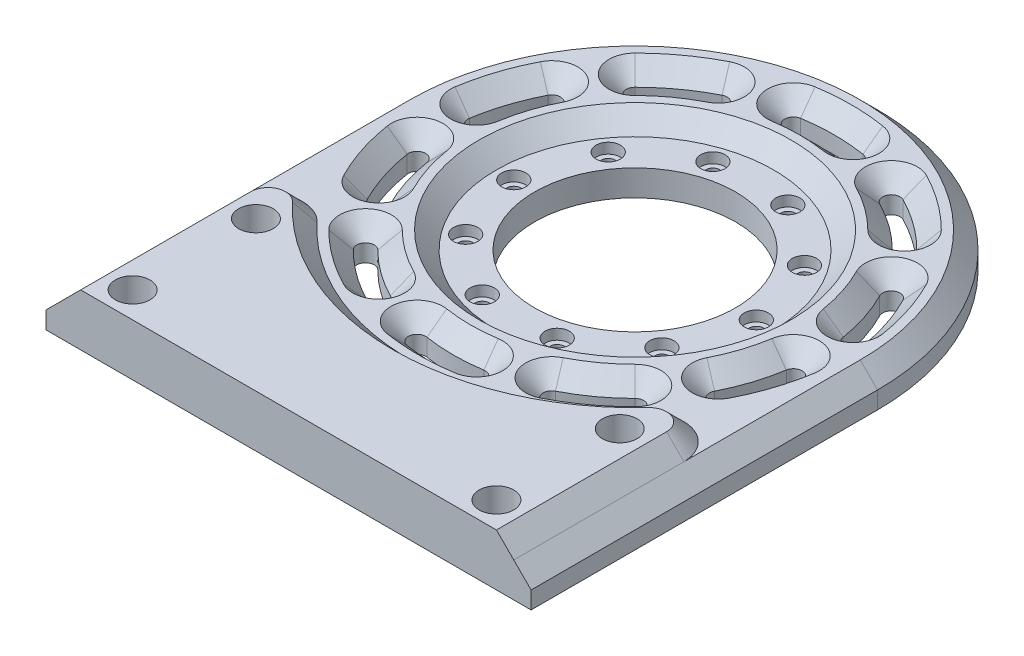
SolidWorks part; units mm, degrees
ref_plane "Front Plane" through (0, 0, 0) normal (0, 0, 1) x (1, 0, 0)
ref_plane "Top Plane" through (0, 0, 0) normal (0, 1, 0) x (1, 0, 0)
ref_plane "Right Plane" through (0, 0, 0) normal (1, 0, 0) x (0, 0, -1)
sketch "Sketch1" plane through (0, 0, 0) normal (0, 1, 0) x (1, 0, 0)
  line L0 (-70, 0) -> (-70, -100)
  line L1 (70, 0) -> (70, -100)
  line L2 (0, -100) -> (70, -100)
  line L3 (0, -100) -> (-70, -100)
  circle A2 centre (0, 0) radius 70
  circle A3 centre (0, 0) radius 29
  circle A4 centre (0, 0) radius 40
  circle A5 centre (-35, 0) radius 2
  circle A6 centre (-28.3156, 20.5725) radius 2
  circle A7 centre (-10.8156, 33.287) radius 2
  circle A8 centre (10.8156, 33.287) radius 2
  circle A9 centre (28.3156, 20.5725) radius 2
  circle A10 centre (35, 0) radius 2
  circle A11 centre (28.3156, -20.5725) radius 2
  circle A12 centre (10.8156, -33.287) radius 2
  circle A13 centre (-10.8156, -33.287) radius 2
  circle A14 centre (-28.3156, -20.5725) radius 2
  circle A15 centre (0, 0) radius 35
  point P36 (0, 0)
  dimension "D1" = 10
extrude "Boss-Extrude2" add sketch "Sketch1" along normal blind 10 contours A12 A15 A11 A10 A9 A8 A7 A6 A5 A14 A13 A3 | A4 A15 A12 A13 A14 A5 A6 A7 A8 A9 A10 A11 | A2 A4 | A2 L0 L3 L2 L1 region at (0, 0, 74.778) region at (0, 0, -68.0201) region at (-38.8686, 0, 0) region at (-32.8564, 0, -2.0832)
sketch "Sketch4" plane through (0, 10, 0) normal (0, 1, 0) x (1, 0, 0)
  circle A0 centre (0, 0) radius 29
  circle A1 centre (0, 0) radius 40
extrude "Cut-Extrude5" cut sketch "Sketch4" against normal blind 5
chamfer "Chamfer11" distance 5 angle 45 4 edges at (70, 10, 50) (0, 10, -70) (-70, 10, 50) (0, 10, 40)
sketch "Sketch7" plane through (0, 10, 0) normal (0, 1, 0) x (1, 0, 0)
  line L0 (0, 0) -> (-55, 0)
  line L1 (0, 0) -> (-28.3156, 20.5725)
  line L2 (-28.3156, 20.5725) -> (-44.4959, 32.3282)
  line L3 (0, 0) -> (-54.3229, 8.6039)
  line L4 (0, 0) -> (-52.3081, 16.9959)
  line L5 (0, 0) -> (-49.0054, 24.9695)
  circle A0 centre (0, 0) radius 55
  arc A1 (-49.0054, 24.9695) -> (-54.3229, 8.6039) centre (0, 0) ccw construction
  arc A2 (-51.2329, 26.1045) -> (-56.7921, 8.995) centre (0, 0) ccw
  arc A3 (-46.7778, 23.8345) -> (-51.8536, 8.2128) centre (0, 0) ccw
  arc A4 (-46.7778, 23.8345) -> (-51.2329, 26.1045) centre (-49.0054, 24.9695) ccw
  arc A5 (-56.7921, 8.995) -> (-51.8536, 8.2128) centre (-54.3229, 8.6039) ccw
  arc A6 (-24.9695, 49.0054) -> (-38.8909, 38.8909) centre (0, 0) ccw construction
  arc A7 (-26.1045, 51.2329) -> (-40.6586, 40.6586) centre (0, 0) ccw
  arc A8 (-23.8345, 46.7778) -> (-37.1231, 37.1231) centre (0, 0) ccw
  arc A9 (-23.8345, 46.7778) -> (-26.1045, 51.2329) centre (-24.9695, 49.0054) ccw
  arc A10 (-40.6586, 40.6586) -> (-37.1231, 37.1231) centre (-38.8909, 38.8909) ccw
  arc A11 (8.6039, 54.3229) -> (-8.6039, 54.3229) centre (0, 0) ccw construction
  arc A12 (8.995, 56.7921) -> (-8.995, 56.7921) centre (0, 0) ccw
  arc A13 (8.2128, 51.8536) -> (-8.2128, 51.8536) centre (0, 0) ccw
  arc A14 (8.2128, 51.8536) -> (8.995, 56.7921) centre (8.6039, 54.3229) ccw
  arc A15 (-8.995, 56.7921) -> (-8.2128, 51.8536) centre (-8.6039, 54.3229) ccw
  arc A16 (38.8909, 38.8909) -> (24.9695, 49.0054) centre (0, 0) ccw construction
  arc A17 (40.6586, 40.6586) -> (26.1045, 51.2329) centre (0, 0) ccw
  arc A18 (37.1231, 37.1231) -> (23.8345, 46.7778) centre (0, 0) ccw
  arc A19 (37.1231, 37.1231) -> (40.6586, 40.6586) centre (38.8909, 38.8909) ccw
  arc A20 (26.1045, 51.2329) -> (23.8345, 46.7778) centre (24.9695, 49.0054) ccw
  arc A21 (54.3229, 8.6039) -> (49.0054, 24.9695) centre (0, 0) ccw construction
  arc A22 (56.7921, 8.995) -> (51.2329, 26.1045) centre (0, 0) ccw
  arc A23 (51.8536, 8.2128) -> (46.7778, 23.8345) centre (0, 0) ccw
  arc A24 (51.8536, 8.2128) -> (56.7921, 8.995) centre (54.3229, 8.6039) ccw
  arc A25 (51.2329, 26.1045) -> (46.7778, 23.8345) centre (49.0054, 24.9695) ccw
  arc A26 (49.0054, -24.9695) -> (54.3229, -8.6039) centre (0, 0) ccw construction
  arc A27 (51.2329, -26.1045) -> (56.7921, -8.995) centre (0, 0) ccw
  arc A28 (46.7778, -23.8345) -> (51.8536, -8.2128) centre (0, 0) ccw
  arc A29 (46.7778, -23.8345) -> (51.2329, -26.1045) centre (49.0054, -24.9695) ccw
  arc A30 (56.7921, -8.995) -> (51.8536, -8.2128) centre (54.3229, -8.6039) ccw
  arc A31 (24.9695, -49.0054) -> (38.8909, -38.8909) centre (0, 0) ccw construction
  arc A32 (26.1045, -51.2329) -> (40.6586, -40.6586) centre (0, 0) ccw
  arc A33 (23.8345, -46.7778) -> (37.1231, -37.1231) centre (0, 0) ccw
  arc A34 (23.8345, -46.7778) -> (26.1045, -51.2329) centre (24.9695, -49.0054) ccw
  arc A35 (40.6586, -40.6586) -> (37.1231, -37.1231) centre (38.8909, -38.8909) ccw
  arc A36 (-8.6039, -54.3229) -> (8.6039, -54.3229) centre (0, 0) ccw construction
  arc A37 (-8.995, -56.7921) -> (8.995, -56.7921) centre (0, 0) ccw
  arc A38 (-8.2128, -51.8536) -> (8.2128, -51.8536) centre (0, 0) ccw
  arc A39 (-8.2128, -51.8536) -> (-8.995, -56.7921) centre (-8.6039, -54.3229) ccw
  arc A40 (8.995, -56.7921) -> (8.2128, -51.8536) centre (8.6039, -54.3229) ccw
  arc A41 (-38.8909, -38.8909) -> (-24.9695, -49.0054) centre (0, 0) ccw construction
  arc A42 (-40.6586, -40.6586) -> (-26.1045, -51.2329) centre (0, 0) ccw
  arc A43 (-37.1231, -37.1231) -> (-23.8345, -46.7778) centre (0, 0) ccw
  arc A44 (-37.1231, -37.1231) -> (-40.6586, -40.6586) centre (-38.8909, -38.8909) ccw
  arc A45 (-26.1045, -51.2329) -> (-23.8345, -46.7778) centre (-24.9695, -49.0054) ccw
  arc A46 (-54.3229, -8.6039) -> (-49.0054, -24.9695) centre (0, 0) ccw construction
  arc A47 (-56.7921, -8.995) -> (-51.2329, -26.1045) centre (0, 0) ccw
  arc A48 (-51.8536, -8.2128) -> (-46.7778, -23.8345) centre (0, 0) ccw
  arc A49 (-51.8536, -8.2128) -> (-56.7921, -8.995) centre (-54.3229, -8.6039) ccw
  arc A50 (-51.2329, -26.1045) -> (-46.7778, -23.8345) centre (-49.0054, -24.9695) ccw
  point P11 (-52.3081, 16.9959)
  point P20 (-32.3282, 44.4959)
  point P27 (0, 55)
  point P34 (32.3282, 44.4959)
  point P41 (52.3081, 16.9959)
  point P48 (52.3081, -16.9959)
  point P55 (32.3282, -44.4959)
  point P62 (0, -55)
  point P69 (-32.3282, -44.4959)
  point P76 (-52.3081, -16.9959)
  point P81 (0, 0)
  dimension "D1" = 9
  dimension "D4" = 10
  dimension "D2" = 9
  dimension "D3" = 9
extrude "Cut-Extrude8" cut sketch "Sketch7" against normal blind 10 contours A8 A10 A7 A9 | A13 A15 A12 A14 | A18 A20 A17 A19 | A22 A25 A23 A24 | A27 A30 A28 A29 | A32 A35 A33 A34 | A37 A40 A38 A39 | A42 A45 A43 A44 | A47 A50 A48 A49 | A2 A5 A3 A4
chamfer "Chamfer16" distance 5 angle 45 40 edges at (-54.6857, 10, 17.7685) (-54.7139, 10, 6.1347) (-47.8704, 10, 27.197) (-49.9305, 10, 16.2234) (-33.7977, 10, 46.5185) (-40.6586, 10, 37.1231) (-22.742, 10, 50.1403) (-30.8587, 10, 42.4734) (0, 10, 57.5) (-11.0731, 10, 53.9318) (11.0731, 10, 53.9318) (0, 10, 52.5) (33.7977, 10, 46.5185) (22.742, 10, 50.1403) (40.6586, 10, 37.1231) (30.8587, 10, 42.4734) (49.9305, 10, 16.2234) (47.8704, 10, 27.197) (54.7139, 10, 6.1347) (54.6857, 10, 17.7685) (49.9305, 10, -16.2234) (54.7139, 10, -6.1347) (47.8704, 10, -27.197) (54.6857, 10, -17.7685) (30.8587, 10, -42.4734) (40.6586, 10, -37.1231) (22.742, 10, -50.1403) (33.7977, 10, -46.5185) (0, 10, -52.5) (11.0731, 10, -53.9318) (-11.0731, 10, -53.9318) (0, 10, -57.5) (-30.8587, 10, -42.4734) (-22.742, 10, -50.1403) (-40.6586, 10, -37.1231) (-33.7977, 10, -46.5185) (-49.9305, 10, -16.2234) (-47.8704, 10, -27.197) (-54.7139, 10, -6.1347) (-54.6857, 10, -17.7685)
sketch "Sketch8" plane through (0, 10, 0) normal (0, 1, 0) x (1, 0, 0)
  line L2 (65, -100) -> (-65, -100) construction
  line L12 (-60, -50.8932) -> (-60, -100)
  line L13 (60, -100) -> (60, -50.8932)
  line L17 (-60, -100) -> (60, -100)
  arc A2 (-51.3333, -47.4939) -> (51.3333, -47.4939) centre (0, 0.0969) ccw
  arc A3 (60, -50.8932) -> (51.3333, -47.4939) centre (55, -50.8932) ccw
  arc A4 (-51.3333, -47.4939) -> (-60, -50.8932) centre (-55, -50.8932) ccw
  dimension "D1" = 5
extrude "Boss-Extrude3" add sketch "Sketch8" along normal blind 5
sketch "Sketch9" plane through (0, 15, 0) normal (0, 1, 0) x (1, 0, 0)
  line L9 (52.5, -56.9118) -> (52.5, -92.5)
  line L10 (52.5, -92.5) -> (-52.5, -92.5)
  line L11 (-52.5, -92.5) -> (-52.5, -56.9118)
  line L12 (52.5, -56.9118) -> (52.5, -92.5)
  line L13 (52.5, -92.5) -> (-52.5, -92.5)
  line L14 (-52.5, -92.5) -> (-52.5, -56.9118)
  circle A9 centre (-52.5, -56.9118) radius 5
  circle A10 centre (52.5, -56.9118) radius 5
  arc A11 (-52.5, -56.9118) -> (52.5, -56.9118) centre (0, 0.0969) ccw
  arc A12 (-52.5, -56.9118) -> (52.5, -56.9118) centre (0, 0.0969) ccw
  circle A13 centre (52.5, -92.5) radius 5
  circle A14 centre (-52.5, -92.5) radius 5
  dimension "D1" = 7.5
extrude "Cut-Extrude9" cut sketch "Sketch9" against normal blind 10 contours L14 A12 A9 | A12 L14 A9 | L14 A14 L13 | L13 A14 L14 | L13 A13 L12 | L12 A13 L13 | A12 A10 L12 | A10 A12 L12 region at (52.7089, 15, 56.4508) region at (51.1613, 15, 59.8666) region at (53.2074, 15, 93.2074) region at (50.3779, 15, 90.3779) region at (-52.7089, 15, 56.4508) region at (-51.1613, 15, 59.8666) region at (-53.2074, 15, 93.2074) region at (-50.3779, 15, 90.3779)
chamfer "Chamfer18" distance 5 angle 45 5 edges at (60, 10, 75.4466) (56.8257, 10, 46.2385) (0, 10, 69.9031) (-56.8257, 10, 46.2385) (-60, 10, 75.4466)
sketch "Sketch12" plane through (0, 5, 0) normal (0, 1, 0) x (1, 0, 0)
  circle A0 centre (-35, 0) radius 3.5
  circle A1 centre (-28.3156, 20.5725) radius 3.5
  circle A2 centre (-10.8156, 33.287) radius 3.5
  circle A3 centre (10.8156, 33.287) radius 3.5
  circle A4 centre (28.3156, 20.5725) radius 3.5
  circle A5 centre (35, 0) radius 3.5
  circle A6 centre (28.3156, -20.5725) radius 3.5
  circle A7 centre (10.8156, -33.287) radius 3.5
  circle A8 centre (-10.8156, -33.287) radius 3.5
  circle A9 centre (-28.3156, -20.5725) radius 3.5
  point P23 (0, 0)
  dimension "D1" = 10
extrude "Cut-Extrude12" cut sketch "Sketch12" against normal blind 3
sketch "Sketch13" plane through (0, 0, 0) normal (0, -1, 0) x (1, 0, 0)
  circle A0 centre (0, 0) radius 29
  circle A1 centre (0, 0) radius 40
  circle A2 centre (0, 0) radius 45
  circle A3 centre (-35, 0) radius 2
  circle A4 centre (-28.3156, 20.5725) radius 2
  circle A5 centre (-10.8156, 33.287) radius 2
  circle A6 centre (10.8156, 33.287) radius 2
  circle A7 centre (28.3156, 20.5725) radius 2
  circle A8 centre (35, 0) radius 2
  circle A9 centre (28.3156, -20.5725) radius 2
  circle A10 centre (10.8156, -33.287) radius 2
  circle A11 centre (-10.8156, -33.287) radius 2
  circle A12 centre (-28.3156, -20.5725) radius 2
  point P28 (0, 0)
  dimension "D1" = 10
extrude "Boss-Extrude4" add sketch "Sketch13" along normal blind 2.5 contours A1 A0 | A2 A1 region at (-38.8686, 0, 0) region at (-43.7272, 0, 0)
